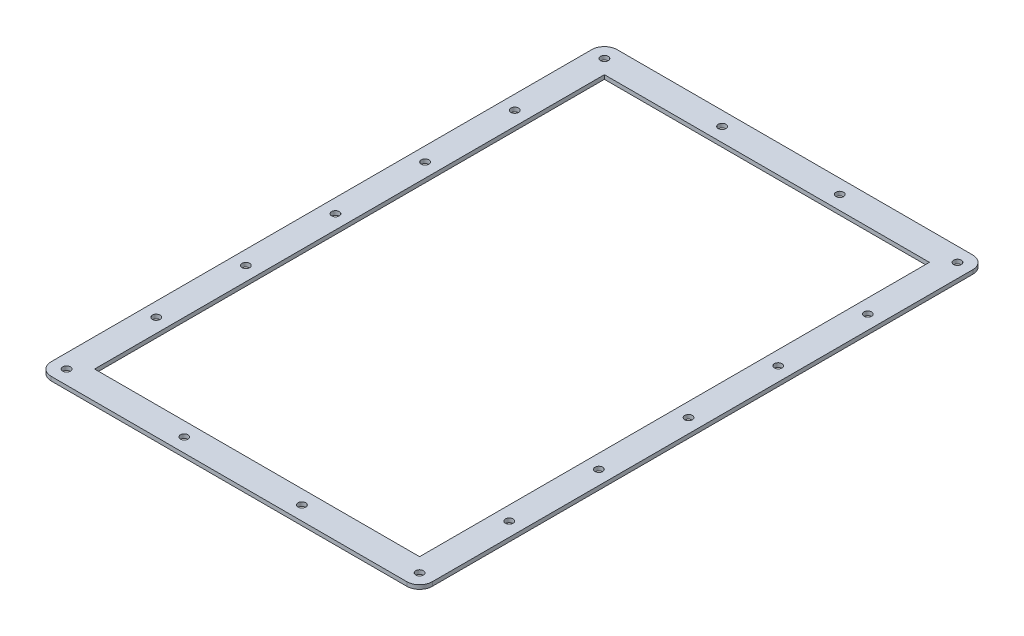
SolidWorks part; units mm, degrees
material "5052-H32"
ref_plane "Front Plane" through (0, 0, 0) normal (0, 0, 1) x (1, 0, 0)
ref_plane "Top Plane" through (0, 0, 0) normal (0, 1, 0) x (1, 0, 0)
ref_plane "Right Plane" through (0, 0, 0) normal (1, 0, 0) x (0, 0, -1)
sketch "Sketch1" plane through (0, 0, 0) normal (0, 1, 0) x (1, 0, 0)
  line L0 (-147, 172) -> (152, 172)
  line L1 (-125, -250) -> (130, -250)
  line L2 (-125, -250) -> (-125, 150)
  line L3 (-125, 150) -> (130, 150)
  line L4 (130, -250) -> (130, 150)
  line L5 (-125, -250) -> (130, 150) construction
  line L6 (-125, 150) -> (130, -250) construction
  line L7 (152, -272) -> (152, 172)
  line L8 (-147, -272) -> (152, -272)
  line L9 (-147, -272) -> (-147, 172)
  line L12 (130, -50) -> (-125, -50) construction
  circle A34 centre (141, 161) radius 3
  circle A35 centre (48.6667, 161) radius 3
  circle A36 centre (-43.6667, 161) radius 3
  circle A37 centre (-136, 161) radius 3
  circle A90 centre (141, 90.6667) radius 3
  circle A91 centre (141, 20.3333) radius 3
  circle A92 centre (141, -50) radius 3
  circle A93 centre (141, -120.3333) radius 3
  circle A94 centre (141, -190.6667) radius 3
  circle A102 centre (-136, 90.6667) radius 3
  circle A103 centre (141, -261) radius 3
  circle A106 centre (-136, 20.3333) radius 3
  circle A107 centre (48.6667, -261) radius 3
  circle A110 centre (-136, -50) radius 3
  circle A111 centre (-43.6667, -261) radius 3
  circle A114 centre (-136, -120.3333) radius 3
  circle A115 centre (-136, -261) radius 3
  circle A118 centre (-136, -190.6667) radius 3
  circle A119 centre (48.6667, -120.3333) radius 3 [skipped]
  circle A120 centre (-43.6667, -120.3333) radius 3 [skipped]
  circle A121 centre (48.6667, 90.6667) radius 3 [skipped]
  circle A122 centre (-43.6667, 90.6667) radius 3 [skipped]
  circle A123 centre (48.6667, 20.3333) radius 3 [skipped]
  circle A124 centre (48.6667, -50) radius 3 [skipped]
  circle A125 centre (-43.6667, -50) radius 3 [skipped]
  circle A126 centre (-43.6667, 20.3333) radius 3 [skipped]
  circle A127 centre (48.6667, -190.6667) radius 3 [skipped]
  circle A128 centre (-43.6667, -190.6667) radius 3 [skipped]
  dimension "D4" = 6
  dimension "D2" = 400
  dimension "D1" = 22
  dimension "D3" = 255
  dimension "D5" = 11
  dimension "D6" = 11
  dimension "D9" = 70.3333
  dimension "D10" = 92.3333
  dimension "D7" = 4
  dimension "D8" = 7
extrude "Boss-Extrude1" add sketch "Sketch1" along normal blind 3.175 contours L9 L8 L7 L0 L4 L1 L2 L3 A34 region at (2.5, 0, -166.6471)
fillet "Fillet1" radius 10 4 edges at (152, 1.5875, 272) (-147, 1.5875, 272) (152, 1.5875, -172) (-147, 1.5875, -172)
equation "\"L\"= 400"
equation "\"W\"= 255"
equation "\"H\"= 110"
equation "\"Compartment Width\"= 80"
equation "\"T\"= 4.7625 * 2 / 3"
equation "\"Inside Fillet Radius\"= 5.55625"
equation "\"Hole\"=15"
equation "\"D2@Sketch1\"=\"L\""
equation "\"D1@Boss-Extrude1\"=\"T\""
equation "\"D3@Sketch1\"=\"W\""
equation "\"D9@Sketch1\"=(\"L\"+22)/6"
equation "\"D10@Sketch1\"=(\"W\"+22)/3"
equation "\"Offset\"= 30"
equation "\"Wheel to Wall\"= 50"
